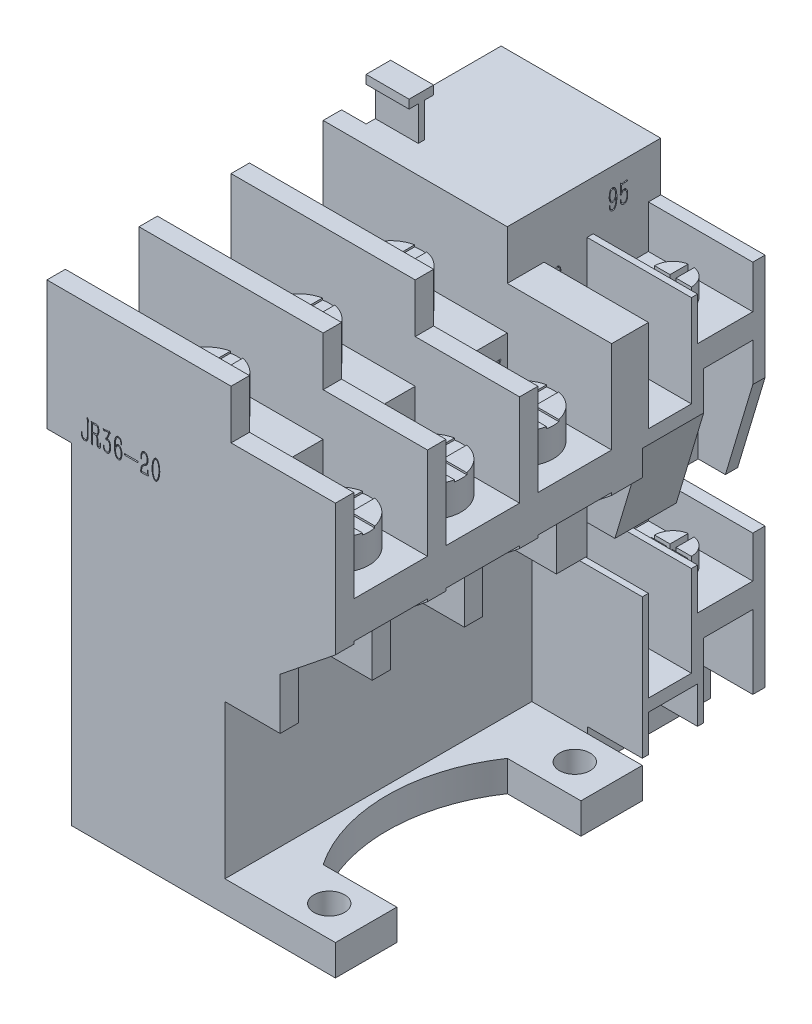
SolidWorks part; units mm, degrees
ref_plane "前视基准面" through (0, 0, 0) normal (0, 0, 1) x (1, 0, 0)
ref_plane "上视基准面" through (0, 0, 0) normal (0, 1, 0) x (1, 0, 0)
ref_plane "右视基准面" through (0, 0, 0) normal (1, 0, 0) x (0, 0, -1)
sketch "草图1" plane through (0, 0, 0) normal (0, 1, 0) x (1, 0, 0)
  line L1 (-23.5, 35) -> (23.5, 35)
  line L2 (-23.5, 35) -> (-23.5, -35)
  line L3 (-23.5, -35) -> (23.5, -35)
  line L4 (23.5, 35) -> (23.5, -35)
  line L5 (-23.5, 35) -> (23.5, -35) construction
  line L6 (-23.5, -35) -> (23.5, 35) construction
  point P0 (0, 0)
  dimension "D1" = 47
  dimension "D2" = 70
extrude "凸台-拉伸1" add sketch "草图1" along normal blind 75
sketch "草图2" plane through (0, 0, 35) normal (0, 0, 1) x (1, 0, 0)
  line L0 (-23.5, 54) -> (-19.5, 54)
  line L1 (-23.5, 75) -> (-23.5, 0) construction
  line L2 (-19.5, 54) -> (-19.5, 0)
  line L3 (-23.5, 0) -> (23.5, 0) construction
  line L4 (-19.5, 0) -> (-23.5, 0)
  line L5 (-23.5, 0) -> (-23.5, 54)
  line L6 (-23.5, 75) -> (23.5, 75) construction
  line L8 (6.5, 67) -> (23.5, 67)
  line L9 (6.5, 67) -> (6.5, 75)
  line L10 (6.5, 75) -> (23.5, 75)
  line L11 (23.5, 67) -> (23.5, 75)
  dimension "D1" = 21
  dimension "D2" = 4
  dimension "D3" = 30
  dimension "D4" = 8
extrude "切除-拉伸1" cut sketch "草图2" against normal blind 75
sketch "草图3" plane through (-23.5, 0, 0) normal (-1, 0, 0) x (0, 0, 1)
  line L0 (-35, 75) -> (35, 75) construction
  line L1 (20, 75) -> (32, 75)
  line L2 (20, 75) -> (20, 54)
  line L3 (20, 54) -> (32, 54)
  line L4 (32, 75) -> (32, 54)
  line L5 (-35, 54) -> (35, 54) construction
  line L6 (35, 75) -> (35, 54) construction
  dimension "D1" = 3
  dimension "D2" = 12
extrude "切除-拉伸2" cut sketch "草图3" against normal blind 4
pattern_linear "阵列(线性)1" count 3 spacing 15 along (0, 0, -1) of "切除-拉伸2"
sketch "草图4" plane through (-23.5, 0, 0) normal (-1, 0, 0) x (0, 0, 1)
  line L0 (-35, 54) -> (-10, 54) construction
  line L1 (-35, 75) -> (-13, 75)
  line L2 (-35, 75) -> (-35, 54)
  line L3 (-35, 54) -> (-13, 54)
  line L4 (-13, 75) -> (-13, 54)
  line L5 (-10, 75) -> (-10, 54) construction
  dimension "D1" = 3
extrude "切除-拉伸3" cut sketch "草图4" against normal blind 4
sketch "草图5" plane through (-19.5, 0, 0) normal (-1, 0, 0) x (0, 0, 1)
  line L0 (2, 54) -> (2, 75) construction
  line L1 (-10, 75) -> (2, 75)
  line L2 (-10, 75) -> (-10, 60)
  line L3 (-10, 60) -> (2, 60)
  line L4 (2, 75) -> (2, 60)
  dimension "D1" = 15
extrude "切除-拉伸4" cut sketch "草图5" against normal blind 45
pattern_linear "阵列(线性)2" count 3 spacing 15 along (0, 0, 1) of "切除-拉伸4"
sketch "草图6" plane through (0, 60, 0) normal (0, 1, 0) x (1, 0, 0)
  line L1 (6.5, -20) -> (23.5, -20)
  line L2 (6.5, -20) -> (6.5, -32)
  line L3 (6.5, -32) -> (23.5, -32)
  line L4 (23.5, -20) -> (23.5, -32)
extrude "切除-拉伸5" cut sketch "草图6" against normal blind 8 contours L2 L3 L4 L1
sketch "草图7" plane through (0, 0, 35) normal (0, 0, 1) x (1, 0, 0)
  line L0 (5.5, 30) -> (14.5, 30)
  line L1 (23.5, 67) -> (23.5, 0) construction
  line L2 (5.5, 30) -> (5.5, 5)
  line L3 (5.5, 5) -> (23.5, 5)
  line L4 (23.5, 5) -> (23.5, 45.5885)
  line L5 (-19.5, 0) -> (-19.5, 54) construction
  line L6 (-19.5, 0) -> (23.5, 0) construction
  line L7 (14.5, 30) -> (14.5, 38.3611)
  line L8 (14.5, 38.3611) -> (23.5, 45.5885)
  dimension "D1" = 25
  dimension "D2" = 5
  dimension "D3" = 25
extrude "切除-拉伸6" cut sketch "草图7" against normal blind 50
pattern_linear "阵列(线性)3" count 3 spacing 15 along (0, 0, -1) of "切除-拉伸5"
sketch "草图8" plane through (0, 0, 0) normal (0, -1, 0) x (1, 0, 0)
  line L0 (23.5, -5) -> (11.5, -5)
  line L1 (23.5, 35) -> (23.5, -35) construction
  line L2 (5.5, -15) -> (23.5, -15) construction
  line L3 (23.5, 25) -> (23.5, -5)
  line L4 (23.5, 25) -> (11.5, 25)
  arc A0 (11.5, 25) -> (11.5, -5) centre (33.7967, 10) ccw
  circle A1 centre (17.5, 30) radius 2.5
  circle A2 centre (17.5, -10) radius 2.5
  dimension "D1" = 10
  dimension "D4" = 5
  dimension "D5" = 5
  dimension "D6" = 5
  dimension "D7" = 5
  dimension "D2" = 12
  dimension "D3" = 12
extrude "切除-拉伸7" cut sketch "草图8" against normal blind 9
sketch "草图9" plane through (0, 30, 0) normal (0, -1, 0) x (1, 0, 0)
  line L1 (5.5, 32) -> (29.5, 32)
  line L2 (5.5, 20) -> (29.5, 20)
  line L3 (29.5, 32) -> (29.5, 20)
  line L4 (5.5, 32) -> (5.5, 20)
  line L5 (5.5, -15) -> (5.5, 35) construction
  dimension "D1" = 24
  dimension "D2" = 24
extrude "切除-拉伸8" cut sketch "草图9" against normal blind 16
pattern_linear "阵列(线性)4" count 3 spacing 15 along (0, 0, -1) of "切除-拉伸8"
sketch "草图10" plane through (0, 60, 0) normal (0, 1, 0) x (1, 0, 0)
  circle A0 centre (-6.5, -26) radius 5
  dimension "D1" = 10
extrude "凸台-拉伸2" add sketch "草图10" along normal blind 6
sketch "草图11" plane through (0, 66, 0) normal (0, 1, 0) x (1, 0, 0)
  line L0 (-5.5, -27) -> (-1.5, -27)
  line L1 (-7.5, -21) -> (-7.5, -25)
  line L2 (-5.5, -27) -> (-5.5, -31)
  line L3 (-11.5, -27) -> (-7.5, -27)
  line L4 (-5.5, -21) -> (-5.5, -25)
  line L5 (-11.5, -25) -> (-7.5, -25)
  line L6 (-11.5, -25) -> (-11.5, -27)
  line L7 (-1.5, -25) -> (-1.5, -27)
  line L8 (-7.5, -21) -> (-5.5, -21)
  line L9 (-7.5, -31) -> (-5.5, -31)
  line L10 (-7.5, -27) -> (-7.5, -31)
  line L11 (-5.5, -25) -> (-1.5, -25)
extrude "切除-拉伸9" cut sketch "草图11" against normal blind 0.3
pattern_linear "阵列(线性)5" count 3 spacing 15 along (0, 0, -1) of "凸台-拉伸2", "切除-拉伸9"
sketch "草图12" plane through (0, 52, 0) normal (0, 1, 0) x (1, 0, 0)
  circle A0 centre (15, -26) radius 5
  dimension "D1" = 10
extrude "凸台-拉伸3" add sketch "草图12" along normal blind 5
sketch "草图13" plane through (0, 57, 0) normal (0, 1, 0) x (1, 0, 0)
  line L0 (16, -27) -> (16, -31)
  line L1 (14, -21) -> (14, -25)
  line L2 (16, -25) -> (20, -25)
  line L3 (10, -27) -> (14, -27)
  line L4 (16, -21) -> (16, -25)
  line L5 (10, -25) -> (14, -25)
  line L6 (16, -21) -> (14, -21)
  line L7 (10, -25) -> (10, -27)
  line L8 (20, -25) -> (20, -27)
  line L9 (14, -31) -> (16, -31)
  line L10 (14, -27) -> (14, -31)
  line L11 (16, -27) -> (20, -27)
extrude "切除-拉伸10" cut sketch "草图13" against normal blind 0.3
pattern_linear "阵列(线性)6" count 3 spacing 15 along (0, 0, -1) of "凸台-拉伸3", "切除-拉伸10"
sketch "草图14" plane through (0, 67, 0) normal (0, 1, 0) x (1, 0, 0)
  line L0 (6.5, 35) -> (6.5, 10) construction
  line L1 (6.5, 33) -> (23.5, 33)
  line L2 (6.5, 33) -> (6.5, 24)
  line L3 (6.5, 24) -> (23.5, 24)
  line L4 (23.5, 33) -> (23.5, 24)
  line L5 (23.5, 35) -> (23.5, 10) construction
  line L6 (6.5, 35) -> (23.5, 35) construction
  dimension "D1" = 2
  dimension "D2" = 9
extrude "切除-拉伸11" cut sketch "草图14" against normal blind 7
pattern_linear "阵列(线性)8" count 2 spacing 38 along (0, -1, 0) of "切除-拉伸11"
sketch "草图15" plane through (0, 0, -35) normal (0, 0, -1) x (-1, 0, 0)
  line L0 (-23.5, 49.7284) -> (-19.0363, 34.7876)
  line L1 (-23.5, 67) -> (-23.5, 0) construction
  line L2 (-19.0363, 34.7876) -> (-6.5, 34.7876)
  line L3 (-6.5, 34.7876) -> (-6.5, 28.7779)
  line L4 (-6.5, 28.7779) -> (-23.5, 28.7779)
  line L5 (-23.5, 28.7779) -> (-23.5, 49.7284)
  line L6 (-23.5, 6) -> (-14.603, 6)
  line L7 (-14.603, 6) -> (-14.603, 0)
  line L8 (-23.5, 0) -> (19.5, 0) construction
  line L9 (-14.603, 0) -> (-23.5, 0)
  line L10 (-23.5, 0) -> (-23.5, 6)
  line L11 (-6.5, 75) -> (-6.5, 67) construction
  point P9 (-6.5, 71)
  dimension "D1" = 6
  dimension "D2" = 0
extrude "切除-拉伸12" cut sketch "草图15" against normal blind 20
sketch "草图16" plane through (0, 6, 0) normal (0, -1, 0) x (1, 0, 0)
  line L0 (23.5, -15) -> (23.5, -35) construction
  line L1 (23.5, -33) -> (14.603, -33)
  line L2 (23.5, -33) -> (23.5, -25)
  line L3 (23.5, -25) -> (14.603, -25)
  line L4 (14.603, -33) -> (14.603, -25)
  line L5 (14.603, -15) -> (14.603, -35) construction
  line L6 (14.603, -35) -> (23.5, -35) construction
  dimension "D1" = 2
  dimension "D2" = 8.897
  dimension "D3" = 8
extrude "切除-拉伸13" cut sketch "草图16" against normal blind 12
pattern_linear "阵列(线性)9" count 2 spacing 38 along (0, 1, 0) of "切除-拉伸13"
sketch "草图17" plane through (0, 44, 0) normal (0, 1, 0) x (1, 0, 0)
  line L0 (23.5, 33) -> (6.5, 33) construction
  line L1 (14.603, 33) -> (21.7886, 33)
  line L2 (14.603, 33) -> (14.603, 25)
  line L3 (14.603, 25) -> (21.7886, 25)
  line L4 (21.7886, 33) -> (21.7886, 25)
  line L5 (21.7886, 33) -> (21.7886, 25) construction
  line L6 (21.7886, 25) -> (14.603, 25) construction
  line L7 (14.603, 25) -> (14.603, 33) construction
  dimension "D1" = 0
  dimension "D2" = 0
  dimension "D3" = 0
extrude "切除-拉伸14" cut sketch "草图17" against normal blind 12
sketch "草图18" plane through (0, 67, 0) normal (0, 1, 0) x (1, 0, 0)
  line L0 (6.5, 24) -> (6.5, 10) construction
  line L1 (6.5, 23) -> (23.5, 23)
  line L2 (6.5, 23) -> (6.5, 16)
  line L3 (6.5, 16) -> (23.5, 16)
  line L4 (23.5, 23) -> (23.5, 16)
  line L5 (23.5, 24) -> (23.5, 10) construction
  line L6 (6.5, 24) -> (23.5, 24) construction
  dimension "D1" = 1
  dimension "D2" = 7
extrude "切除-拉伸15" cut sketch "草图18" against normal blind 15
pattern_linear "阵列(线性)10" count 2 spacing 38 along (0, -1, 0) of "切除-拉伸15"
sketch "草图19" plane through (0, 52, 0) normal (0, 1, 0) x (1, 0, 0)
  line L0 (14.5, 19) -> (14.5, 16.542)
  line L1 (12.042, 19) -> (14.5, 19)
  line L2 (15.5, 20) -> (17.958, 20)
  line L3 (14.5, 22.458) -> (14.5, 20)
  line L4 (12.042, 20) -> (14.5, 20)
  line L5 (15.5, 22.458) -> (15.5, 20)
  line L6 (15.5, 19) -> (15.5, 16.542)
  line L7 (15.5, 19) -> (17.958, 19)
  arc A0 (12.042, 19) -> (14.5, 16.542) centre (15, 19.5) ccw
  arc A1 (14.5, 22.458) -> (12.042, 20) centre (15, 19.5) ccw
  arc A2 (15.5, 16.542) -> (17.958, 19) centre (15, 19.5) ccw
  arc A3 (17.958, 20) -> (15.5, 22.458) centre (15, 19.5) ccw
  dimension "D1" = 6
extrude "凸台-拉伸5" add sketch "草图19" along normal blind 3
pattern_linear "阵列(线性)11" count 2 spacing 38 along (0, -1, 0) of "凸台-拉伸5"
sketch "草图20" plane through (0, 6, 0) normal (0, -1, 0) x (1, 0, 0)
  line L0 (14.603, -15) -> (14.603, -25) construction
  line L1 (14.603, -16) -> (23.5, -16)
  line L2 (14.603, -16) -> (14.603, -24)
  line L3 (14.603, -24) -> (23.5, -24)
  line L4 (23.5, -16) -> (23.5, -24)
  line L5 (23.5, -15) -> (23.5, -25) construction
  line L6 (23.5, -25) -> (14.603, -25) construction
  dimension "D1" = 1
  dimension "D2" = 8
extrude "切除-拉伸16" cut sketch "草图20" against normal blind 6
sketch "草图21" plane through (0, 60, 0) normal (0, 1, 0) x (1, 0, 0)
  line L0 (14.5135, 31.4603) -> (14.5135, 28.5)
  line L1 (14.5135, 28.5) -> (12, 28.5)
  line L3 (12.0586, 27.9099) -> (14.5135, 27.9099)
  line L4 (14.5135, 27.9099) -> (14.5135, 25.5397)
  line L6 (15.4865, 25.5397) -> (15.4865, 27.9099)
  line L7 (15.4865, 27.9099) -> (17.9414, 27.9099)
  line L9 (18, 28.5) -> (15.4865, 28.5)
  line L10 (15.4865, 28.5) -> (15.4865, 31.4603)
  arc A0 (18, 28.5) -> (15.4865, 31.4603) centre (15, 28.5) ccw
  arc A1 (14.5135, 31.4603) -> (12, 28.5) centre (15, 28.5) ccw
  arc A2 (12.0586, 27.9099) -> (14.5135, 25.5397) centre (15, 28.5) ccw
  arc A3 (15.4865, 25.5397) -> (17.9414, 27.9099) centre (15, 28.5) ccw
  dimension "D1" = 6
extrude "凸台-拉伸6" add sketch "草图21" along normal blind 3
pattern_linear "阵列(线性)12" count 2 spacing 38 along (0, -1, 0) of "凸台-拉伸6"
sketch "草图22" plane through (0, 75, 0) normal (0, 1, 0) x (1, 0, 0)
  line L0 (-19.5, 13) -> (-19.5, 35) construction
  line L1 (-19.5, 17) -> (-12.5, 17)
  line L2 (-19.5, 17) -> (-19.5, 13)
  line L3 (-19.5, 13) -> (-12.5, 13)
  line L4 (-12.5, 17) -> (-12.5, 13)
  line L5 (-19.5, 13) -> (-23.5, 13) construction
  dimension "D1" = 0
  dimension "D2" = 4
  dimension "D3" = 7
extrude "凸台-拉伸7" add sketch "草图22" along normal blind 7
sketch "草图23" plane through (-12.5, 0, 0) normal (1, 0, 0) x (0, 0, -1)
  line L0 (13, 80.5887) -> (14.5, 80.5887)
  line L1 (13, 82) -> (13, 75) construction
  line L2 (14.5, 80.5887) -> (14.5, 75)
  line L3 (13, 75) -> (17, 75) construction
  line L4 (14.5, 75) -> (13, 75)
  line L5 (13, 75) -> (13, 80.5887)
  line L6 (17, 80.5887) -> (15.5, 80.5887)
  line L7 (17, 82) -> (17, 75) construction
  line L8 (15.5, 80.5887) -> (15.5, 75)
  line L9 (15.5, 75) -> (17, 75)
  line L10 (17, 75) -> (17, 80.5887)
  dimension "D1" = 1.5
  dimension "D2" = 1.5
extrude "切除-拉伸17" cut sketch "草图23" against normal blind 7
sketch "草图24" plane through (0, 65.7, 0) normal (0, 1, 0) x (1, 0, 0)
  point P0 (-6.5, -26)
  point P1 (-6.5, -11)
  point P3 (-6.5, 4)
sketch "草图25" plane through (0, 56.7, 0) normal (0, 1, 0) x (1, 0, 0)
  point P0 (15, -26)
  point P1 (15, -11)
  point P3 (15, 4)
sketch "3_1_Point" plane through (0, 52, 0) normal (0, 1, 0) x (1, 0, 0)
  point P0 (15, 19.5)
sketch "3_0_Point" plane through (0, 60, 0) normal (0, 1, 0) x (1, 0, 0)
  point P0 (15, 28.5)
sketch "4_1_Point" plane through (0, 22, 0) normal (0, 1, 0) x (1, 0, 0)
  point P0 (15, 28.5)
sketch "4_0_Point" plane through (0, 14, 0) normal (0, 1, 0) x (1, 0, 0)
  point P0 (15, 19.5)
sketch "草图30" plane through (0, 60, 0) normal (0, 1, 0) x (1, 0, 0)
  text T0 "\r\n 1/LI  "
  text T1 "\r\n 3/L2"
  text T2 "\r\n 5/L3"
extrude "切除-拉伸18" cut sketch "草图30" against normal blind 0.3
sketch "草图31" plane through (6.5, 0, 0) normal (1, 0, 0) x (0, 0, -1)
  text T0 "\r\n 2/T1"
  text T1 "\r\n 4/T2"
  text T2 "    \r\n  6/T3"
extrude "切除-拉伸19" cut sketch "草图31" against normal blind 0.3
sketch "草图32" plane through (6.5, 0, 0) normal (1, 0, 0) x (0, 0, -1)
  text T0 "\r\n         95\r\n   96\r\n\r\n\r\n\r\n\r\n        98\r\n    97"
extrude "切除-拉伸20" cut sketch "草图32" against normal blind 0.3
sketch "草图33" plane through (0, 0, 35) normal (0, 0, 1) x (1, 0, 0)
  text T0 "  \r\n\r\n\r\n   JR36-20"
extrude "切除-拉伸21" cut sketch "草图33" against normal blind 0.3
sketch "草图34" plane through (23.5, 0, 0) normal (1, 0, 0) x (0, 0, -1)
  point P0 (28.796, 21.0386)
sketch "0_0_Point" plane through (0, 65.7, 0) normal (0, 1, 0) x (1, 0, 0)
  point P0 (-6.5, -26)
other "0_0" parameters "直径"=2, "端头长度"=2
ref_axis "基准轴1" through (-6.5, 75.7, 26) along (0, -1, 0)
sketch "0_1_Point" plane through (0, 56.7, 0) normal (0, 1, 0) x (1, 0, 0)
  point P0 (15, -26)
other "0_1" parameters "直径"=2, "端头长度"=2
ref_axis "基准轴2" through (15, 66.7, 26) along (0, -1, 0)
sketch "1_0_Point" plane through (0, 65.7, 0) normal (0, 1, 0) x (1, 0, 0)
  point P0 (-6.5, -11)
other "1_0" parameters "直径"=2, "端头长度"=2
ref_axis "基准轴3" through (-6.5, 75.7, 11) along (0, -1, 0)
sketch "1_1_Point" plane through (0, 56.7, 0) normal (0, 1, 0) x (1, 0, 0)
  point P0 (15, -11)
other "1_1" parameters "直径"=2, "端头长度"=2
ref_axis "基准轴4" through (15, 66.7, 11) along (0, -1, 0)
sketch "2_0_Point" plane through (0, 65.7, 0) normal (0, 1, 0) x (1, 0, 0)
  point P0 (-6.5, 4)
other "2_0" parameters "直径"=2, "端头长度"=2
ref_axis "基准轴5" through (-6.5, 75.7, -4) along (0, -1, 0)
sketch "2_1_Point" plane through (0, 56.7, 0) normal (0, 1, 0) x (1, 0, 0)
  point P0 (15, 4)
other "2_1" parameters "直径"=2, "端头长度"=2
ref_axis "基准轴6" through (15, 66.7, -4) along (0, -1, 0)
other "3_0" parameters "直径"=2, "端头长度"=2
ref_axis "基准轴7" through (15, 70, -28.5) along (0, -1, 0)
other "3_1" parameters "直径"=2, "端头长度"=2
ref_axis "基准轴8" through (15, 62, -19.5) along (0, -1, 0)
other "4_0" parameters "直径"=2, "端头长度"=2
ref_axis "基准轴9" through (15, 24, -19.5) along (0, -1, 0)
other "4_1" parameters "直径"=2, "端头长度"=2
ref_axis "基准轴10" through (15, 32, -28.5) along (0, -1, 0)
